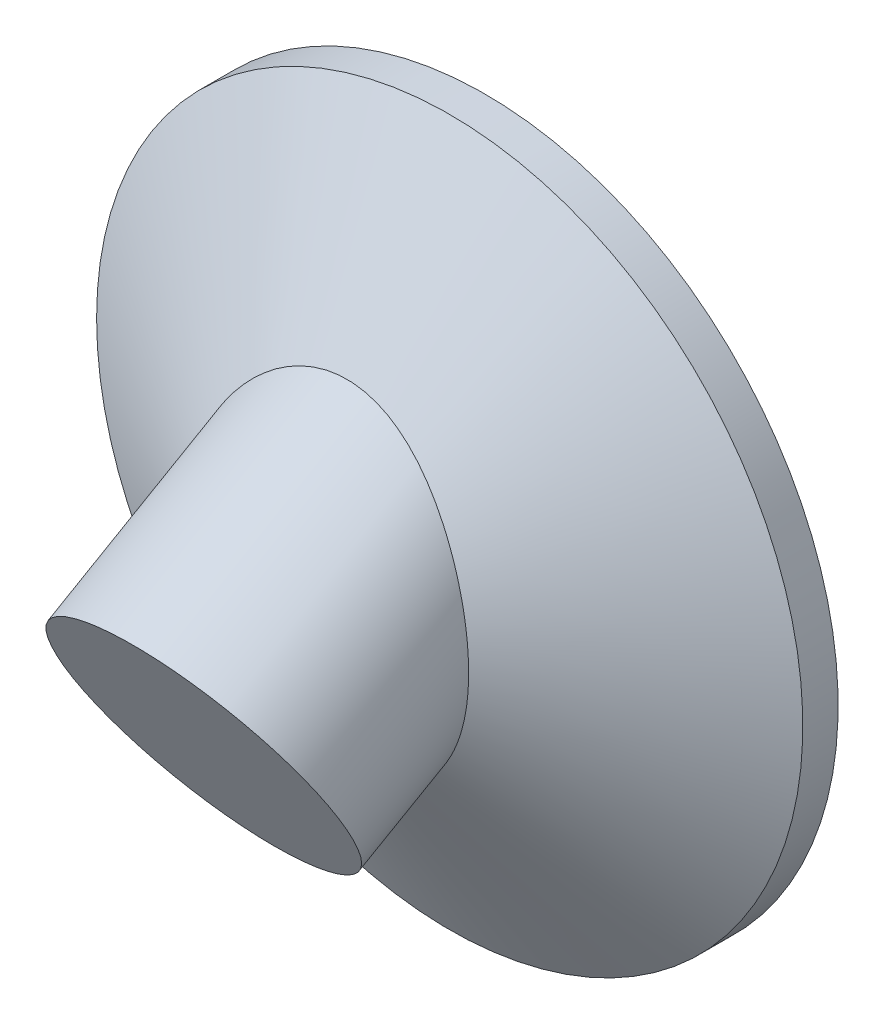
SolidWorks part; units mm, degrees
note: '?' marks a value the reader was unsure of.
material "HGA"
ref_plane "Front Plane" through (0, 0, 0) normal (0, 0, 1) x (1, 0, 0)
ref_plane "Top Plane" through (0, 0, 0) normal (0, 1, 0) x (1, 0, 0)
ref_plane "Right Plane" through (0, 0, 0) normal (1, 0, 0) x (0, 0, -1)
sketch "Sketch2" plane through (0, 0, 0) normal (0, 1, 0) x (1, 0, 0)
  line L0 (0, 819.0384) -> (0, -450.844) construction
  line L1 (-1000, -50) -> (-1000, 50)
  line L2 (-1000, -50) -> (-393.7822, -400)
  line L3 (-393.7822, -400) -> (0, -400)
  line L4 (-1000, 50) -> (-393.7822, 400)
  line L5 (-393.7822, 400) -> (0, 400)
  line L6 (-1000, 0) -> (0, 0) construction
  point P3 (0, 0)
  point P12 (0, 234.1138)
  point P13 (-1000, 162.6323)
  point P14 (0, 0)
  dimension "D1" = 2000
  dimension "D2" = 800
  dimension "D3" = 150
  dimension "D4" = 100
revolve "Revolve-Thin1" add sketch "Sketch2" angle 360 about L0
ref_axis "Axis1" through (-1100, 0, 400) along (1, 0, 0)?
ref_plane "Plane1" through (0, -173.2051, 300) normal (0, -0.5, 0.866) x (1, 0, 0)
ref_plane "Plane2" through (0, -373.2051, 646.4102) normal (0, -0.5, 0.866) x (1, 0, 0)
sketch "Sketch3" plane through (0, -373.2051, 646.4102) normal (0, -0.5, 0.866) x (1, 0, 0)
  line L0 (-1100, 200) -> (1100, 200) construction
  circle A0 centre (0, 200) radius 400
  dimension "D1" = 800
extrude "Boss-Extrude1" add sketch "Sketch3" against normal up to surface up to face at (-1000, 0, 50)
